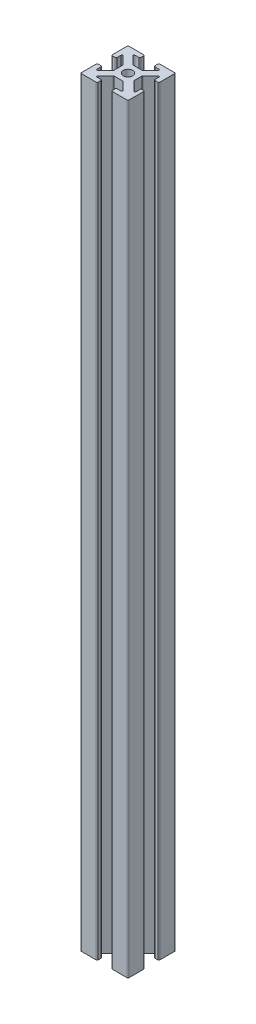
SolidWorks part; units mm, degrees
ref_plane "Plan de face" through (0, 0, 0) normal (0, 0, 1) x (1, 0, 0)
ref_plane "Plan de dessus" through (0, 0, 0) normal (0, 1, 0) x (1, 0, 0)
ref_plane "Plan de droite" through (0, 0, 0) normal (1, 0, 0) x (0, 0, -1)
sketch "Esquisse1" plane through (0, 0, 0) normal (0, 1, 0) x (1, 0, 0)
  line L0 (0, 0) -> (20, 0) construction
  line L1 (20, 0) -> (20, 20) construction
  line L2 (20, 20) -> (0, 20) construction
  line L3 (0, 20) -> (0, 0) construction
  line L4 (0, 0) -> (20, 20) construction
  line L5 (20, 20) -> (0, 20) construction
  line L6 (0, 20) -> (20, 0) construction
  line L7 (0, 0) -> (0, 7)
  line L8 (0, 20) -> (0, 13)
  line L9 (0, 20) -> (7, 20)
  line L10 (20, 20) -> (20, 13)
  line L11 (20, 20) -> (13, 20)
  line L12 (20, 0) -> (20, 7)
  line L13 (20, 0) -> (13, 0)
  line L14 (0, 0) -> (7, 0)
  line L15 (0, 7) -> (2, 7)
  line L16 (0, 13) -> (2, 13)
  line L17 (2, 13) -> (2, 16)
  line L18 (7, 0) -> (7, 2)
  line L19 (13, 0) -> (13, 2)
  line L20 (13, 2) -> (16, 2)
  line L21 (20, 7) -> (18.5, 7)
  line L22 (18.5, 7) -> (18.5, 4)
  line L23 (20, 13) -> (18, 13)
  line L24 (18, 13) -> (18, 16)
  line L25 (13, 20) -> (13, 18)
  line L26 (13, 18) -> (16, 18)
  line L27 (7, 20) -> (7, 18)
  line L28 (7, 18) -> (4, 18)
  line L29 (10, 10) -> (10, 14) construction
  line L30 (10, 14) -> (14, 14) construction
  line L31 (14, 14) -> (14, 6) construction
  line L32 (14, 6) -> (6, 6) construction
  line L33 (6, 6) -> (6, 14) construction
  line L34 (6, 14) -> (10, 14) construction
  line L42 (7, 2) -> (4, 2)
  line L44 (2, 7) -> (2, 4)
  line L49 (2, 4) -> (6, 8)
  line L50 (4, 2) -> (8, 6)
  line L51 (8, 6) -> (12, 6)
  line L52 (12, 6) -> (16, 2)
  line L53 (2, 16) -> (6, 12)
  line L54 (6, 12) -> (6, 8)
  line L55 (18.5, 4) -> (14, 8.5)
  line L56 (14, 8.5) -> (14, 12)
  line L57 (14, 12) -> (18, 16)
  line L58 (16, 18) -> (12, 14)
  line L59 (12, 14) -> (8, 14)
  line L60 (8, 14) -> (4, 18)
  circle A0 centre (10, 10) radius 2
extrude "Boss.-Extru.1" add sketch "Esquisse1" along normal blind 320
fillet "Congé1" radius 0.4 36 edges at (4, 160, -18) (2, 160, -16) (6, 160, -12) (6, 160, -8) (2, 160, -4) (2, 160, -7) (0, 160, -7) (0, 160, 0) (7, 160, 0) (7, 160, -2) (4, 160, -2) (8, 160, -6) (12, 160, -6) (16, 160, -2) (13, 160, -2) (13, 160, 0) (20, 160, 0) (20, 160, -7) (18.5, 160, -7) (18.5, 160, -4) (14, 160, -8.5) (14, 160, -12) (18, 160, -16) (18, 160, -13) (20, 160, -13) (20, 160, -20) (13, 160, -20) (13, 160, -18) (16, 160, -18) (12, 160, -14) (8, 160, -14) (7, 160, -18) (7, 160, -20) (0, 160, -20) (0, 160, -13) (2, 160, -13) first distance on face at (6, 160, -16) first distance on face at (2, 160, -14.5) first distance on face at (4, 160, -14) first distance on face at (6, 160, -10) first distance on face at (4, 160, -6) first distance on face at (2, 160, -5.5) first distance on face at (1, 160, -7) first distance on face at (0, 160, -3.5) first distance on face at (3.5, 160, 0) first distance on face at (7, 160, -1) first distance on face at (5.5, 160, -2) first distance on face at (6, 160, -4) first distance on face at (10, 160, -6) first distance on face at (14, 160, -4) first distance on face at (14.5, 160, -2) first distance on face at (13, 160, -1) first distance on face at (16.5, 160, 0) first distance on face at (20, 160, -3.5) first distance on face at (19.25, 160, -7) first distance on face at (18.5, 160, -5.5) first distance on face at (16.25, 160, -6.25) first distance on face at (14, 160, -10.25) first distance on face at (16, 160, -14) first distance on face at (18, 160, -14.5) first distance on face at (19, 160, -13) first distance on face at (20, 160, -16.5) first distance on face at (16.5, 160, -20) first distance on face at (13, 160, -19) first distance on face at (14.5, 160, -18) first distance on face at (14, 160, -16) first distance on face at (10, 160, -14) first distance on face at (5.5, 160, -18) first distance on face at (7, 160, -19) first distance on face at (3.5, 160, -20) first distance on face at (0, 160, -16.5) first distance on face at (1, 160, -13)
sketch "Esquisse2" plane through (0, 0, 0) normal (0, 0, 1) x (1, 0, 0)
  line L0 (0, 0) -> (20, 0) construction
  line L1 (0, 0) -> (0, 85) construction
  line L2 (0, 320) -> (0, 0) construction
  line L3 (0, 85) -> (10, 85) construction
  line L4 (10, 85) -> (10, 73) construction
  line L5 (10, 73) -> (10, 51) construction
  circle A0 centre (10, 73) radius 2
  circle A1 centre (10, 51) radius 2
  dimension "D4" = 12
  dimension "D1" = 85
  dimension "D2" = 20
  dimension "D3" = 10
  dimension "D5" = 22
extrude "Enlèv. mat.-Extru.1" cut sketch "Esquisse2" against normal through all both and the other way through all
sketch "Esquisse3" plane through (0, 0, 0) normal (0, 0, 1) x (1, 0, 0)
  line L0 (0, 0) -> (20, 0) construction
  line L1 (10, 0) -> (10, 90) construction
  line L3 (10, 90) -> (10, 180) construction
  circle A0 centre (10, 90) radius 2
  circle A2 centre (10, 180) radius 2
  circle A3 centre (10, 220) radius 2 construction
  dimension "D1" = 90
  dimension "D4" = 40
  dimension "D2" = 90
sketch "Esquisse4" plane through (0, 0, 0) normal (0, 0, 1) x (1, 0, 0)
  line L0 (10, 0) -> (10, 150) construction
  line L1 (8.1657, 0) -> (11.8343, 0) construction
  line L2 (10, 150) -> (10, 139) construction
  line L3 (10, 139) -> (10, 117) construction
  circle A0 centre (10, 139) radius 2
  circle A1 centre (10, 117) radius 2
  dimension "D3" = 22
  dimension "D1" = 150
  dimension "D2" = 11
extrude "Enlèv. mat.-Extru.2" cut sketch "Esquisse4" against normal through all both and the other way through all
extrude "Enlèv. mat.-Extru.3" cut sketch "Esquisse3" against normal through all
sketch "Esquisse5" plane through (0, 0, -6) normal (0, 0, 1) x (1, 0, 0)
  line L0 (10, 0) -> (10, 217) construction
  line L1 (8.1657, 0) -> (11.8343, 0) construction
  line L2 (10, 217) -> (10, 195) construction
  circle A0 centre (10, 217) radius 2
  circle A1 centre (10, 195) radius 2
  dimension "D1" = 217
  dimension "D2" = 22
extrude "Enlèv. mat.-Extru.4" cut sketch "Esquisse5" against normal through all
